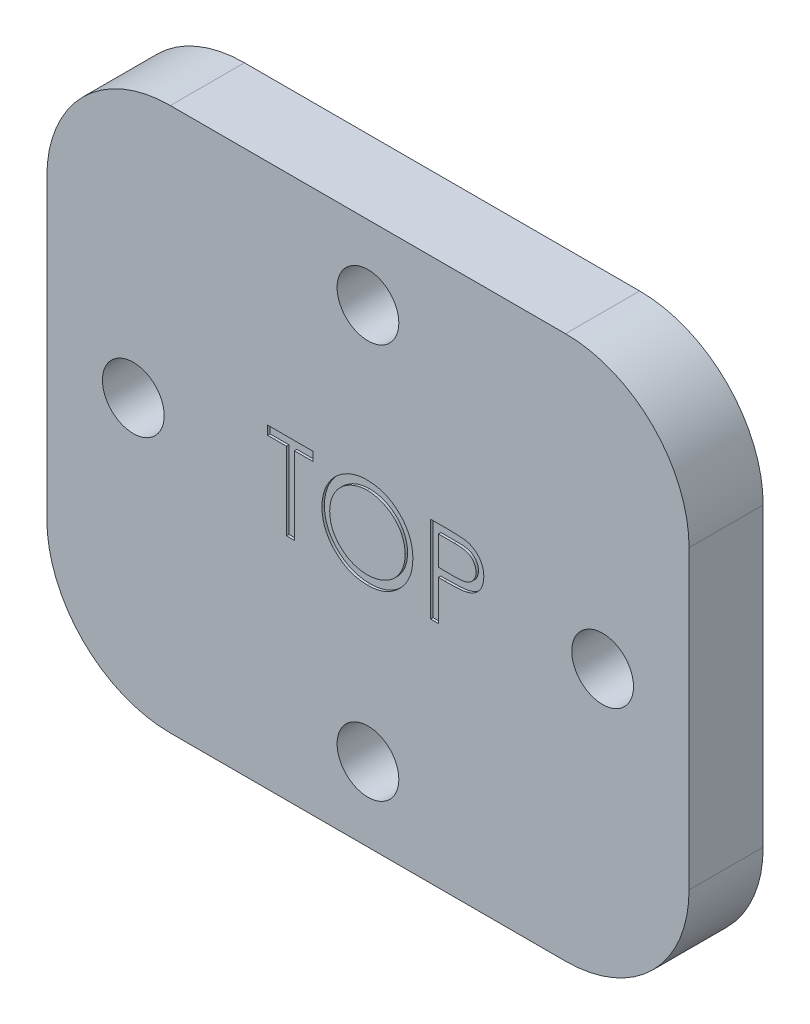
SolidWorks part; units mm, degrees
material "6061-T6 (SS)"
ref_plane "Front Plane" through (0, 0, 0) normal (0, 0, 1) x (1, 0, 0)
ref_plane "Top Plane" through (0, 0, 0) normal (0, 1, 0) x (1, 0, 0)
ref_plane "Right Plane" through (0, 0, 0) normal (1, 0, 0) x (0, 0, -1)
ref_axis "X" through (-88.99, 0, 0) along (1, 0, 0)
ref_axis "Y" through (0, 55, 0) along (0, -1, 0)
ref_axis "Z" through (0, 0, -88.99) along (0, 0, 1)
sketch "Sketch1" plane through (0, 0, 0) normal (0, 0, 1) x (1, 0, 0)
  line L0 (-9.5, 0) -> (9.5, 0) construction
  line L1 (-13, 11) -> (13, 11)
  line L2 (-13, 11) -> (-13, -11)
  line L3 (-13, -11) -> (13, -11)
  line L4 (13, 11) -> (13, -11)
  line L5 (-13, 11) -> (13, -11) construction
  line L6 (-13, -11) -> (13, 11) construction
  line L7 (0, -8) -> (0, 8) construction
  circle A0 centre (0, 8) radius 1.25
  circle A1 centre (9.5, 0) radius 1.25
  circle A2 centre (0, -8) radius 1.25
  circle A3 centre (-9.5, 0) radius 1.25
  point P0 (0, 0)
  point P14 (0, 0)
  point P15 (0, 0)
  point P16 (12.5289, 0)
  dimension "D1" = 26
  dimension "D3" = 2.5
  dimension "D2" = 22
  dimension "D4" = 19
  dimension "D5" = 16
extrude "Boss-Extrude1" add sketch "Sketch1" along normal blind 3
fillet "Fillet1" radius 5 4 edges at (-13, -11, 1.5) (13, -11, 1.5) (13, 11, 1.5) (-13, 11, 1.5)
sketch "Sketch2" plane through (0, 0, 3) normal (0, 0, 1) x (1, 0, 0)
  line L0 (-4.1053, -1.7337) -> (4.2995, -1.7337) construction
  text T0 "TOP"
  point P3 (4.2995, -1.6782)
  point P4 (0, 0)
  point P5 (-2.7461, -1.4563)
  point P6 (-3.606, -1.4008)
  point P7 (-4.1053, -1.7337)
  point P8 (0, 0)
  point P9 (0, 0)
  point P10 (0, 0)
extrude "Cut-Extrude1" cut sketch "Sketch2" against normal blind 0.1
